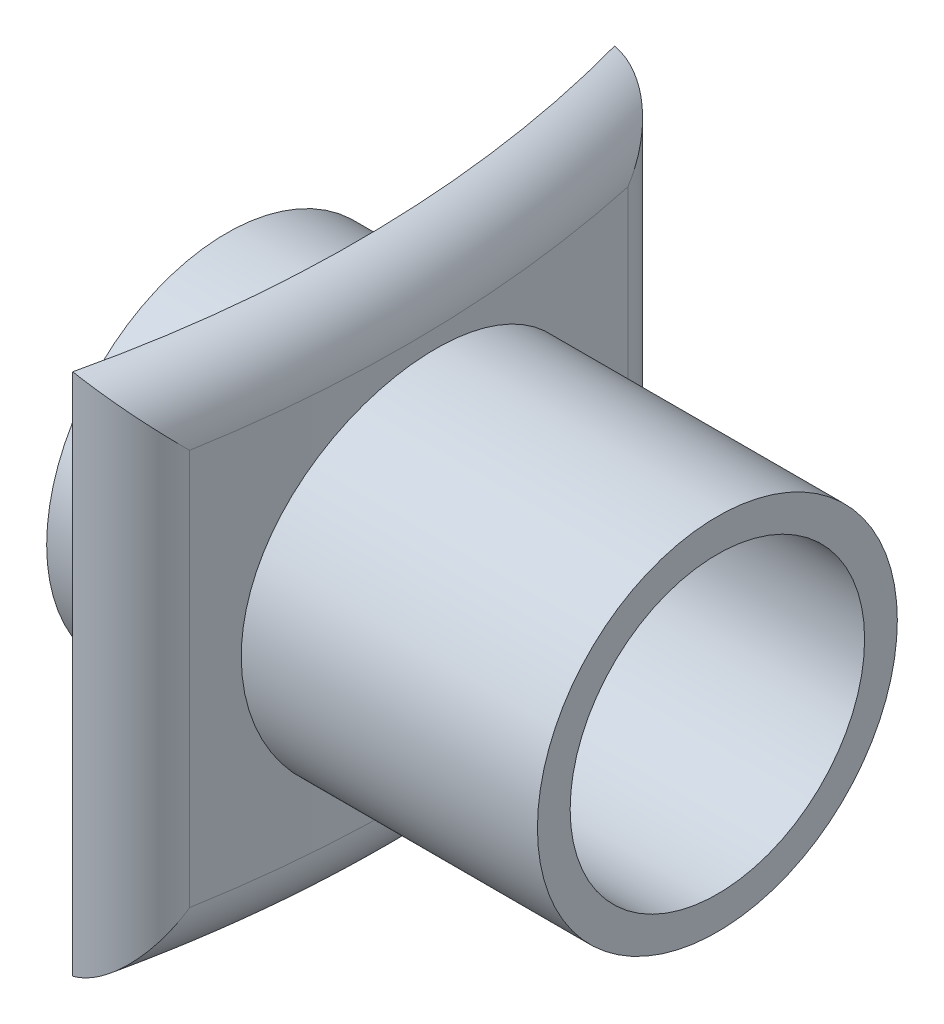
SolidWorks part; units mm, degrees
ref_plane "Front Plane" through (0, 0, 0) normal (0, 0, 1) x (1, 0, 0)
ref_plane "Top Plane" through (0, 0, 0) normal (0, 1, 0) x (1, 0, 0)
ref_plane "Right Plane" through (0, 0, 0) normal (1, 0, 0) x (0, 0, -1)
sketch "Sketch3" plane through (0, 0, 0) normal (1, 0, 0) x (0, 0, -1)
  circle A0 centre (0, 0) radius 5.5
  circle A1 centre (0, 0) radius 3.3
  dimension "D1" = 11
  dimension "D2" = 6.6
extrude "Boss-Extrude3" add sketch "Sketch3" along normal blind 15 contours A1 | A0 region at (0, 0, 0)
sketch "Sketch6" plane through (0, 0, 0) normal (0, 1, 0) x (1, 0, 0)
  line L1 (3.4775, 8.3808) -> (4.92, 8.9783)
  line L2 (3.8195, -8.5225) -> (5.27, -9.1233)
  arc A0 (3.8195, -8.5225) -> (3.4775, 8.3808) centre (-29.5351, -0.7421) ccw
  arc A1 (5.27, -9.1233) -> (4.92, 8.9783) centre (-29.5351, -0.7421) ccw
  circle A2 centre (-29.5351, -0.7421) radius 34.25 construction
  circle A3 centre (-29.5351, -0.7421) radius 35.8 construction
  dimension "D1" = 1.55
extrude "Boss-Extrude4" add sketch "Sketch6" along normal blind 8 and the other way blind 8 contours L2 A1 L1 A0
sketch "Sketch7" plane through (0, 0, 0) normal (-1, 0, 0) x (0, 0, 1)
  circle A0 centre (0, 0) radius 4.5
  dimension "D1" = 9
extrude "Cut-Extrude1" cut sketch "Sketch7" against normal up to surface (15 mm away) from offset 1 up to face at (15, 0, -5.5) offset against normal yes
fillet "Fillet2" radius 2 4 edges at (6.2582, 8, 0.05) (4.92, 0, -8.9783) (6.2582, -8, 0.05) (5.27, 0, 9.1233)
